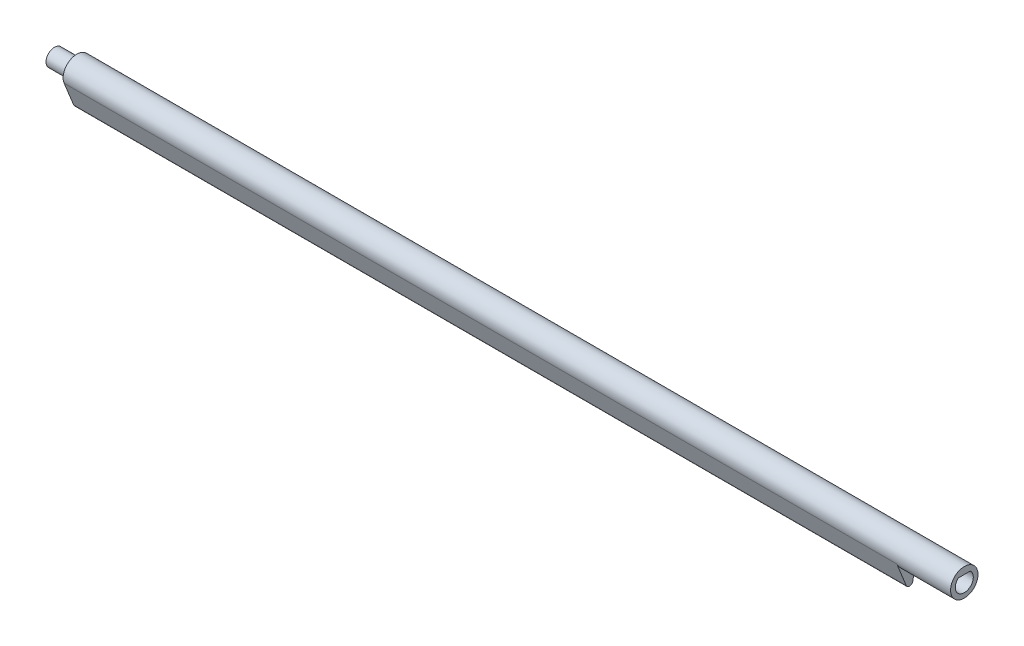
SolidWorks part; units mm, degrees
ref_plane "Front Plane" through (0, 0, 0) normal (0, 0, 1) x (1, 0, 0)
ref_plane "Top Plane" through (0, 0, 0) normal (0, 1, 0) x (1, 0, 0)
ref_plane "Right Plane" through (0, 0, 0) normal (1, 0, 0) x (0, 0, -1)
sketch "Sketch1" plane through (0, 0, 0) normal (1, 0, 0) x (0, 0, -1)
  line L1 (0, 0) -> (0, 42.2576) construction
  line L4 (-3.7081, 6.5) -> (-0.927, -0.375)
  line L5 (4, 8) -> (2, 6.2594)
  line L6 (2, 6.2594) -> (0.9878, -0.1559)
  arc A0 (-3.7081, 6.5) -> (0, 12) centre (0, 8) cw
  arc A1 (4, 8) -> (0, 12) centre (0, 8) ccw
  arc A2 (0.9878, -0.1559) -> (-0.927, -0.375) centre (0, 0) cw
  dimension "D2" = 4
  dimension "D3" = 1
  dimension "D1" = 8
  dimension "D4" = 2
  dimension "D5" = 140
extrude "Boss-Extrude1" add sketch "Sketch1" along normal mid plane 243
sketch "Sketch2" plane through (-121.5, 0, 0) normal (-1, 0, 0) x (0, 0, 1)
  circle A0 centre (0, 8) radius 2.5
  dimension "D1" = 5
extrude "Boss-Extrude2" add sketch "Sketch2" along normal blind 6.5
sketch "Sketch3" plane through (121.5, 0, 0) normal (1, 0, 0) x (0, 0, -1)
  circle A0 centre (0, 8) radius 2.625
  circle A1 centre (0, 8) radius 4
  dimension "D1" = 5.25
  dimension "D2" = 8
extrude "Boss-Extrude3" add sketch "Sketch3" along normal blind 16
sketch "Sketch4" plane through (137.5, 0, 0) normal (1, 0, 0) x (0, 0, -1)
  line L0 (-1.7292, 9.975) -> (1.7292, 9.975)
  circle A0 centre (0, 8) radius 2.625 construction
  circle A1 centre (0, 8) radius 2.625
  circle M4 centre (0, 8) radius 2.625
  dimension "D1" = 4.6
extrude "Boss-Extrude4" add sketch "Sketch4" against normal up to surface (16 mm away) contours L0 M4 region at (137.5, 10.238, 0) up to face at (121.5, 8, -2.625)
fillet "Fillet1" radius 2 2 edges at (121.5, 7.1297, -3) (121.5, 5.3201, -1.8518)
